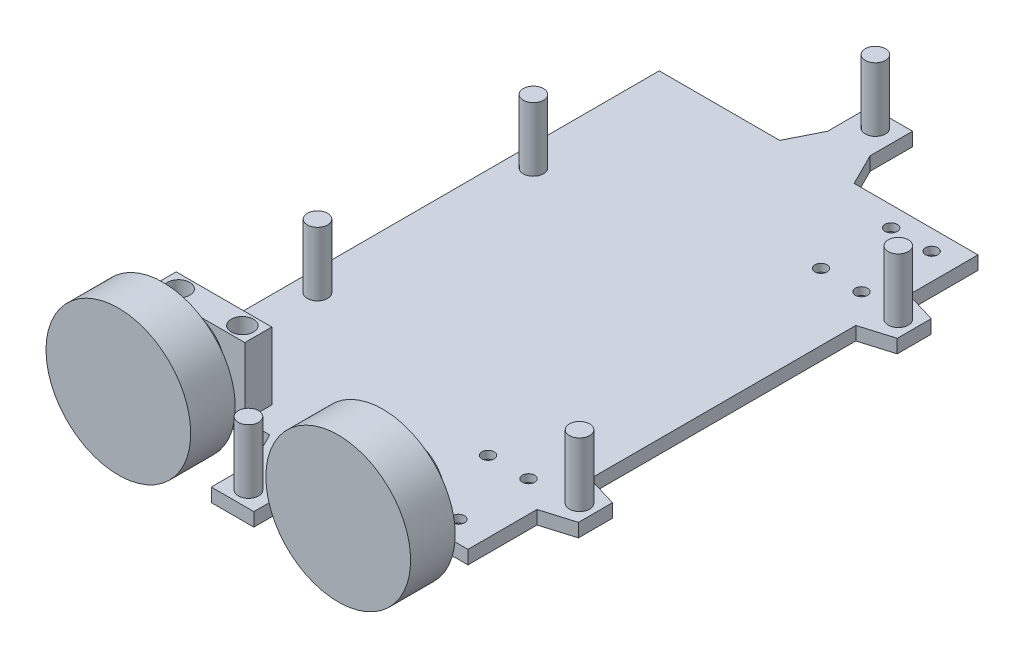
SolidWorks part; units mm, degrees
ref_plane "Front Plane" through (0, 0, 0) normal (0, 0, 1) x (1, 0, 0)
ref_plane "Top Plane" through (0, 0, 0) normal (0, 1, 0) x (1, 0, 0)
ref_plane "Right Plane" through (0, 0, 0) normal (1, 0, 0) x (0, 0, -1)
sketch "Sketch1" plane through (0, 0, 0) normal (0, 1, 0) x (1, 0, 0)
  line L0 (-87.7927, 0) -> (87.7927, 0) construction
  line L5 (-87.7927, 165.1) -> (87.7927, 165.1)
  line L6 (-87.7927, 165.1) -> (-87.7927, -165.1)
  line L7 (-87.7927, -165.1) -> (87.7927, -165.1)
  line L8 (87.7927, 165.1) -> (87.7927, -165.1)
  line L9 (0, 165.1) -> (0, -165.1) construction
  line L10 (-87.7927, 101.6) -> (-392.5927, 101.6)
  line L11 (-87.7927, -101.6) -> (-392.5927, -101.6)
  line L12 (-392.5927, -101.6) -> (-346.8735, -81.6)
  line L13 (-346.8735, -81.6) -> (-346.8735, -90.3491)
  line L14 (-346.8735, -90.3491) -> (-317.1033, -90.3491)
  line L15 (-317.1033, -90.3491) -> (-297.1033, -81.6)
  line L16 (-297.1033, -81.6) -> (-297.1033, -90.3491)
  line L17 (-297.1033, -90.3491) -> (-267.3331, -90.3491)
  line L18 (-267.3331, -90.3491) -> (-247.3331, -81.6)
  line L19 (-247.3331, -81.6) -> (-247.3331, -90.3491)
  line L20 (-247.3331, -90.3491) -> (-217.5629, -90.3491)
  line L21 (-217.5629, -90.3491) -> (-197.5629, -81.6)
  line L22 (-197.5629, -81.6) -> (-197.5629, -90.3491)
  line L23 (-197.5629, -90.3491) -> (-167.7927, -90.3491)
  line L24 (-167.7927, -90.3491) -> (-137.7927, -81.6)
  line L25 (-137.7927, -81.6) -> (-137.7927, -90.3491)
  line L26 (-137.7927, -90.3491) -> (-87.7927, -90.3491)
  line L27 (-137.7927, 90.3491) -> (-87.7927, 90.3491)
  line L28 (-197.5629, 90.3491) -> (-167.7927, 90.3491)
  line L29 (-137.7927, 81.6) -> (-137.7927, 90.3491)
  line L30 (-167.7927, 90.3491) -> (-137.7927, 81.6)
  line L31 (-197.5629, 81.6) -> (-197.5629, 90.3491)
  line L32 (-217.5629, 90.3491) -> (-197.5629, 81.6)
  line L33 (-247.3331, 90.3491) -> (-217.5629, 90.3491)
  line L34 (-247.3331, 81.6) -> (-247.3331, 90.3491)
  line L35 (-267.3331, 90.3491) -> (-247.3331, 81.6)
  line L36 (-297.1033, 90.3491) -> (-267.3331, 90.3491)
  line L37 (-297.1033, 81.6) -> (-297.1033, 90.3491)
  line L38 (-317.1033, 90.3491) -> (-297.1033, 81.6)
  line L39 (-346.8735, 90.3491) -> (-317.1033, 90.3491)
  line L40 (-346.8735, 81.6) -> (-346.8735, 90.3491)
  line L41 (-392.5927, 101.6) -> (-346.8735, 81.6)
  line L42 (78.4937, -130.8116) -> (78.4937, -151.8116)
  line L43 (-77.9683, 151.8116) -> (-27.1683, 151.8116)
  line L44 (-77.9683, 151.8116) -> (-77.9683, 130.8116)
  line L45 (-77.9683, 130.8116) -> (-27.1683, 130.8116)
  line L46 (-27.1683, 151.8116) -> (-27.1683, 130.8116)
  line L47 (27.6937, 130.8116) -> (78.4937, 130.8116)
  line L48 (27.6937, 130.8116) -> (27.6937, 151.8116)
  line L49 (27.6937, 151.8116) -> (78.4937, 151.8116)
  line L50 (78.4937, 130.8116) -> (78.4937, 151.8116)
  line L51 (27.6937, -151.8116) -> (78.4937, -151.8116)
  line L52 (27.6937, -130.8116) -> (27.6937, -151.8116)
  line L53 (27.6937, -130.8116) -> (78.4937, -130.8116)
  line L54 (-27.1683, -151.8116) -> (-27.1683, -130.8116)
  line L55 (-77.9683, -130.8116) -> (-27.1683, -130.8116)
  line L56 (-77.9683, -151.8116) -> (-77.9683, -130.8116)
  line L57 (-77.9683, -151.8116) -> (-27.1683, -151.8116)
  line L58 (53.0937, 157.0084) -> (53.0937, 28.6084) construction
  line L59 (34.0437, 112.3084) -> (72.1437, 112.3084)
  line L60 (34.0437, 112.3084) -> (34.0437, 28.6084)
  line L61 (34.0437, 28.6084) -> (72.1437, 28.6084)
  line L62 (72.1437, 112.3084) -> (72.1437, 28.6084)
  line L63 (46.2787, 112.3084) -> (59.9087, 112.3084)
  line L64 (46.2787, 112.3084) -> (46.2787, 157.0084)
  line L65 (46.2787, 157.0084) -> (59.9087, 157.0084)
  line L66 (59.9087, 112.3084) -> (59.9087, 157.0084)
  line L67 (46.2787, -157.0084) -> (59.9087, -157.0084)
  line L68 (-15.9616, 13.0957) -> (67.0384, 13.0957)
  line L69 (-15.9616, 13.0957) -> (-15.9616, -24.9043)
  line L70 (-15.9616, -24.9043) -> (67.0384, -24.9043)
  line L71 (67.0384, 13.0957) -> (67.0384, -24.9043)
  line L72 (-80.3064, 106.623) -> (-46.3064, 106.623)
  line L73 (-80.3064, 106.623) -> (-80.3064, 66.623)
  line L74 (-80.3064, 66.623) -> (-46.3064, 66.623)
  line L75 (-46.3064, 106.623) -> (-46.3064, 66.623)
  line L76 (53.0937, -157.0084) -> (53.0937, -28.6084) construction
  line L77 (59.9087, -112.3084) -> (59.9087, -157.0084)
  line L78 (46.2787, -112.3084) -> (46.2787, -157.0084)
  line L79 (46.2787, -112.3084) -> (59.9087, -112.3084)
  line L80 (72.1437, -112.3084) -> (72.1437, -28.6084)
  line L81 (34.0437, -28.6084) -> (72.1437, -28.6084)
  line L82 (34.0437, -112.3084) -> (34.0437, -28.6084)
  line L83 (34.0437, -112.3084) -> (72.1437, -112.3084)
  line L84 (-46.3064, -106.623) -> (-46.3064, -66.623)
  line L85 (-80.3064, -66.623) -> (-46.3064, -66.623)
  line L86 (-80.3064, -106.623) -> (-80.3064, -66.623)
  line L87 (-80.3064, -106.623) -> (-46.3064, -106.623)
  line L88 (-75.0927, 152.4) -> (75.0927, 152.4)
  line L89 (75.0927, 152.4) -> (75.0927, -152.4)
  line L90 (-75.0927, -152.4) -> (75.0927, -152.4)
  line L91 (-75.0927, 152.4) -> (-75.0927, -152.4)
  line L92 (53.0937, 28.6084) -> (53.0937, -28.6084) construction
  dimension "D1" = 304.8
  dimension "D2" = 203.2
  dimension "D3" = 21
  dimension "D4" = 50.8
  dimension "D5" = 330.2
  dimension "D6" = 20
  dimension "D7" = 20
  dimension "D8" = 30
  dimension "D9" = 50
  dimension "D10" = 38.1
  dimension "D11" = 83.7
  dimension "D12" = 44.7
  dimension "D13" = 13.63
  dimension "D14" = 175.5853
  dimension "D15" = 83
  dimension "D16" = 38
  dimension "D17" = 34
  dimension "D18" = 40
  dimension "D19" = 12.7
sketch "Sketch6" plane through (0, 0, 0) normal (0, 0, 1) x (1, 0, 0)
  line L0 (34.0437, 19.05) -> (72.1437, -19.05) construction
  line L1 (34.0437, 19.05) -> (72.1437, 19.05)
  line L2 (34.0437, 19.05) -> (34.0437, -19.05)
  line L3 (34.0437, -19.05) -> (72.1437, -19.05)
  line L4 (72.1437, 19.05) -> (72.1437, -19.05)
  line L5 (34.0437, -19.05) -> (72.1437, 19.05) construction
  line L6 (53.0937, 0) -> (-203.3411, 0) construction
  line L7 (-87.7927, 0) -> (-392.5927, 0) construction
  circle A0 centre (53.0937, 0) radius 34.05
  point P6 (53.0937, 0)
  dimension "D2" = 15
  dimension "D3" = 68.1
  dimension "D1" = 38.1
sketch "Sketch3" plane through (0, 0, 0) normal (0, 1, 0) x (1, 0, 0)
  line L0 (-87.7927, 0) -> (87.7927, 0) construction
  line L1 (-75, 120) -> (75, 120)
  line L2 (-75, 120) -> (-75, -120)
  line L3 (-75, -120) -> (75, -120)
  line L4 (75, 120) -> (75, -120)
  line L5 (0, 0) -> (0, 48.434) construction
  line L6 (43.5687, 110.5679) -> (62.6187, 110.5679) construction
  line L7 (43.5687, 110.5679) -> (43.5687, 77.5479) construction
  line L8 (43.5687, 77.5479) -> (62.6187, 77.5479) construction
  line L9 (62.6187, 110.5679) -> (62.6187, 77.5479) construction
  line L10 (53.0937, 110.5679) -> (53.0937, 77.5479) construction
  line L11 (53.0937, 157.0084) -> (53.0937, 28.6084) construction
  line L12 (41.425, -110) -> (60.475, -110) construction
  line L13 (41.425, -110) -> (41.425, -76.98) construction
  line L14 (60.475, -110) -> (60.475, -76.98) construction
  line L15 (41.425, -76.98) -> (60.475, -76.98) construction
  line L16 (31.9, -73.98) -> (70, -73.98) construction
  line L17 (31.9, -73.98) -> (31.9, -113) construction
  line L18 (31.9, -113) -> (70, -113) construction
  line L19 (70, -73.98) -> (70, -113) construction
  line L20 (16.9, -136) -> (85, -136)
  line L21 (-52.5, -107.3) -> (-52.5, -120) construction
  line L22 (-75, -120) -> (-30, -120)
  line L23 (-75, -120) -> (-75, -107.3)
  line L24 (-75, -107.3) -> (-30, -107.3)
  line L25 (-30, -120) -> (-30, -107.3)
  line L26 (16.9, -136) -> (16.9, -157)
  line L27 (-58.85, -113.65) -> (-46.15, -113.65) construction
  line L28 (-58.85, -113.65) -> (-58.85, -120) construction
  line L29 (-58.85, -120) -> (-46.15, -120)
  line L30 (-46.15, -113.65) -> (-46.15, -120) construction
  line L31 (50.95, -73.98) -> (50.95, -113) construction
  line L32 (16.9, -157) -> (85, -157)
  line L33 (85, -136) -> (85, -157)
  line L34 (19.0437, 0) -> (87.1437, 0) construction
  line L35 (50.95, -136) -> (50.95, -157)
  line L36 (-86.55, -136) -> (-18.45, -136)
  line L37 (-86.55, -136) -> (-86.55, -157)
  line L38 (-86.55, -157) -> (-18.45, -157)
  line L39 (-18.45, -136) -> (-18.45, -157)
  line L40 (-52.5, -136) -> (-52.5, -157)
  line L41 (-30, -113.65) -> (-37.5, -113.65) construction
  line L42 (-52.5, -123) -> (-52.5, -136)
  line L43 (-68.75, -136) -> (-36.25, -136)
  line L44 (-68.75, -136) -> (-68.75, -123)
  line L45 (-68.75, -123) -> (-36.25, -123)
  line L46 (-36.25, -136) -> (-36.25, -123)
  line L47 (34.7, -136) -> (67.2, -136)
  line L48 (34.7, -136) -> (34.7, -123)
  line L49 (34.7, -123) -> (67.2, -123)
  line L50 (67.2, -136) -> (67.2, -123)
  line L51 (50.95, -123) -> (50.95, -136)
  circle A0 centre (-67.5, -113.65) radius 2.5
  circle A1 centre (-67.5, -113.65) radius 4.75 construction
  circle A2 centre (-37.5, -113.65) radius 2.5
  dimension "D10" = 5
  dimension "D11" = 9.5
  dimension "D12" = 15
  dimension "D1" = 33.02
  dimension "D2" = 19.05
  dimension "D3" = 3
  dimension "D4" = 3
  dimension "D5" = 12.7
  dimension "D6" = 6.35
  dimension "D7" = 12.7
  dimension "D8" = 10
  dimension "D9" = 0
  dimension "D13" = 45
  dimension "D14" = 0
  dimension "D15" = 38.1
  dimension "D16" = 19.05
  dimension "D17" = 68.1
  dimension "D18" = 68.1
  dimension "D19" = 240
  dimension "D20" = 150
  dimension "D21" = 5
  dimension "D22" = 39.02
  dimension "D23" = 33.02
  dimension "D24" = 13
  dimension "D25" = 21
  dimension "D26" = 32.5
  dimension "D27" = 3
extrude "Boss-Extrude1" add sketch "Sketch3" against normal blind 6.35 from vertex contours L3 L4 L1 L2 starting at point (34.0437, -19.05, 0)
hole_wizard "CBORE for M5 SBHCS1" positions "Sketch4" profile "Sketch5" counterbore size "M5" standard "ANSI Metric" end condition through all
sketch "Sketch4" plane through (0, -25.4, 0) normal (0, 1, 0) x (1, 0, 0)
  point P0 (60.475, -76.98)
  point P3 (41.425, -76.98)
  point P6 (41.425, -110)
  point P9 (60.475, -110)
  point P12 (62.6187, 77.5479)
  point P15 (43.5687, 77.5479)
  point P18 (62.6187, 110.5679)
  point P21 (43.5687, 110.5679)
sketch "Sketch5" plane through (60.475, -25.4, 76.98) normal (1, 0, 0) x (0, 0, -1)
  line L0 (0, 0) -> (0, 6.35)
  line L1 (0, 6.35) -> (2.9, 6.35)
  line L3 (2.9, 6.35) -> (2.9, 2.75)
  line L4 (2.9, 2.75) -> (5.25, 2.75)
  line L5 (5.25, 2.75) -> (5.25, 0)
  line L7 (5.25, 0) -> (0, 0)
  line L11 (0, -6.35) -> (0, 107.95) construction
  dimension "Thru Hole Dia." = 5.8
  dimension "Thru Hole Depth" = 6.35
  dimension "C'Bore Dia." = 10.5
  dimension "C'Bore Depth" = 2.75
extrude "Boss-Extrude2" add sketch "Sketch3<4>" along normal blind 31.75 from surface separate body contours L23 L24 L25 L22 starting at face at (60.475, -19.05, 74.08)
sketch "Sketch3<4>" plane through (0, 0, 0) normal (0, 1, 0) x (1, 0, 0) same geometry as "Sketch3"
hole_wizard "CBORE for M5 SBHCS2" positions "Sketch7" profile "Sketch8" counterbore size "M5" standard "ANSI Metric" end condition through all
sketch "Sketch7" plane through (0, 12.7, 0) normal (0, 1, 0) x (1, 0, 0)
  point P0 (-37.5, -113.65)
  point P3 (-67.5, -113.65)
sketch "Sketch8" plane through (-37.5, 12.7, 113.65) normal (1, 0, 0) x (0, 0, 1)
  line L0 (0, 0) -> (0, 38.1)
  line L1 (0, 38.1) -> (2.9, 38.1)
  line L3 (2.9, 38.1) -> (2.9, 12.75)
  line L4 (2.9, 12.75) -> (5.25, 12.75)
  line L5 (5.25, 12.75) -> (5.25, 0)
  line L7 (5.25, 0) -> (0, 0)
  line L11 (0, -6.35) -> (0, 107.95) construction
  dimension "Thru Hole Dia." = 5.8
  dimension "Thru Hole Depth" = 38.1
  dimension "C'Bore Dia." = 10.5
  dimension "C'Bore Depth" = 12.75
hole_wizard "3/8-16 Tapped Hole1" positions "Sketch9" profile "Sketch10" tap size "3/8-16" standard "ANSI Inch" end condition through all
sketch "Sketch9" plane through (0, 0, 120) normal (0, 0, 1) x (1, 0, 0)
  point P0 (-52.5, 0)
sketch "Sketch10" plane through (-52.5, 0, 120) normal (1, 0, 0) x (0, -1, 0)
  line L0 (0, 0) -> (0, 240)
  line L1 (0, 240) -> (3.9687, 240)
  line L2 (3.9687, 240) -> (3.9687, 0)
  line L5 (3.9687, 0) -> (0, 0)
  line L11 (0, -6.35) -> (0, 107.95) construction
  dimension "Thru Tap Drill Dia." = 7.9375
  dimension "Thru Tap Drill Depth" = 240
cosmetic thread "Hole Thread1" parameters "D2"=9.525
hole_wizard "1/2 (0.5) Diameter Hole1" positions "Sketch11" profile "Sketch12" hole size "1/2" standard "ANSI Inch"
sketch "Sketch11" plane through (0, 0, 120) normal (0, 0, 1) x (1, 0, 0)
  point P0 (-52.5, 0)
sketch "Sketch12" plane through (-52.5, 0, 120) normal (1, 0, 0) x (0, -1, 0)
  line L0 (0, 0) -> (0, 10.1655)
  line L1 (0, 10.1655) -> (6.35, 6.35)
  line L2 (6.35, 6.35) -> (6.35, 0)
  line L5 (6.35, 0) -> (0, 0)
  line L10 (0, 10.1655) -> (-6.35, 6.35) construction
  line L11 (0, -6.35) -> (0, 107.95) construction
  dimension "Hole Dia." = 12.7
  dimension "Hole Depth" = 6.35
  dimension "Drill Angle" = 118
sketch "Sketch13" plane through (0, 0, 0) normal (0, 1, 0) x (1, 0, 0)
  line L0 (53.0937, 0) -> (-203.3411, 0) construction
  line L1 (0, 0) -> (-119.925, 0) construction
  line L2 (-75, 120) -> (-75, -120) construction
  line L3 (75, 120) -> (75, -120) construction
  line L4 (75, -87.5) -> (90, -83)
  line L5 (90, -83) -> (90, -67)
  line L6 (90, -67) -> (75, -62.5)
  line L7 (75, -75) -> (90, -75) construction
  line L9 (75, -62.5) -> (75, -87.5)
  line L10 (-52.5, -107.3) -> (-52.5, -91.4601) construction
  line L11 (50.95, -113) -> (50.95, -100.3386) construction
  line L14 (-0.775, -120) -> (-0.775, -155) construction
  line L15 (-75, -120) -> (75, -120) construction
  line L16 (-18.275, -120) -> (-10.775, -135)
  line L17 (-10.775, -135) -> (-10.775, -155)
  line L18 (-10.775, -155) -> (9.225, -155)
  line L19 (9.225, -155) -> (9.225, -135)
  line L20 (9.225, -135) -> (16.725, -120)
  line L21 (-18.275, -120) -> (16.725, -120)
  line L22 (75, 75) -> (90, 75) construction
  line L23 (75, 62.5) -> (75, 87.5)
  line L24 (90, 67) -> (75, 62.5)
  line L25 (90, 83) -> (90, 67)
  line L26 (75, 87.5) -> (90, 83)
  line L27 (-0.775, 120) -> (-0.775, 155) construction
  line L28 (-18.275, 120) -> (16.725, 120)
  line L29 (9.225, 135) -> (16.725, 120)
  line L30 (9.225, 155) -> (9.225, 135)
  line L31 (-10.775, 155) -> (9.225, 155)
  line L32 (-10.775, 135) -> (-10.775, 155)
  line L33 (-18.275, 120) -> (-10.775, 135)
  line L34 (50.95, -73.98) -> (50.95, -113) construction
  circle A1 centre (-65, 0) radius 4.7625 construction
  circle A3 centre (82.5, -75) radius 4.7625
  circle A5 centre (-65, -50.8) radius 4.7625
  circle A6 centre (-65, 50.8) radius 4.7625
  circle A7 centre (-0.775, -147.5) radius 4.7625
  circle A8 centre (82.5, 75) radius 4.7625
  circle A9 centre (-0.775, 147.5) radius 4.7625
  point P27 (-10.9265, -135)
  point P28 (0, 0)
  point P29 (-17.6866, -120)
  dimension "D1" = 9.525
  dimension "D2" = 10
  dimension "D3" = 16
  dimension "D4" = 50.8
  dimension "D5" = 25
  dimension "D6" = 15
  dimension "D7" = 75
  dimension "D8" = 15
  dimension "D9" = 35
  dimension "D10" = 20
  dimension "D11" = 20
  dimension "D12" = 7.5
extrude "Boss-Extrude3" add sketch "Sketch13" against normal up to surface (25.4 mm away) from surface contours L31 L30 L29 L28 L33 L32 | L26 L25 L24 L23 | L6 L9 L4 L5 | L19 L20 L21 L16 L17 L18 up to face at (60.475, -25.4, 71.73) starting at face at (60.475, -19.05, 74.08)
revolve "Revolve1" add sketch "Sketch3<5>" angle 360 about L42 region at (-69.525, 0, 146.5) region at (-60.625, 0, 129.5)
sketch "Sketch3<5>" plane through (0, 0, 0) normal (0, 1, 0) x (1, 0, 0) same geometry as "Sketch3"
revolve "Revolve2" add sketch "Sketch3<6>" angle 360 about L51 region at (33.925, 0, 146.5) region at (42.825, 0, 129.5)
sketch "Sketch3<6>" plane through (0, 0, 0) normal (0, 1, 0) x (1, 0, 0) same geometry as "Sketch3"
extrude "Boss-Extrude4" add sketch "Sketch13<4>" along normal blind 30 from surface separate body contours A7 | A5 | A3 | A8 | A9 | A6 starting at face at (60.475, -19.05, 74.08)
sketch "Sketch13<4>" plane through (0, 0, 0) normal (0, 1, 0) x (1, 0, 0) same geometry as "Sketch13"
sketch "Sketch16" plane through (0, 0, 0) normal (0, 1, 0) x (1, 0, 0)
  line L0 (-86.0009, 0) -> (95.4028, 0) construction
  line L2 (-86.0009, 0) -> (-86.0009, -124.6)
  line L3 (53.0937, 0) -> (-203.3411, 0) construction
  line L4 (-86.0009, 0) -> (-76.0009, 0)
  line L5 (-76.0009, 0) -> (-76.0009, -27.6435)
  line L6 (-76.0009, -27.6435) -> (-49.9164, -39.0555)
  line L7 (-49.9164, -39.0555) -> (-49.9164, -62.5445)
  line L8 (-49.9164, -62.5445) -> (-76.946, -74.3699)
  line L9 (-76.946, -74.3699) -> (-76.946, -126.7142)
  line L10 (-65, -50.8) -> (-49.9164, -50.8) construction
  line L11 (-103.2039, -160.6854) -> (-103.2039, -133.7611)
  line L12 (-103.2039, -160.6854) -> (-87.7174, -173.4309)
  line L13 (-87.7174, -173.4309) -> (81.4985, -173.4309)
  line L14 (-103.2039, -133.7611) -> (-86.0009, -124.6)
  line L15 (-76.946, -126.7142) -> (-95.4282, -136.5564)
  line L16 (-95.4282, -136.5564) -> (-95.4282, -158.6101)
  line L17 (-95.4282, -158.6101) -> (-84.4257, -167.6652)
  line L18 (-84.4257, -167.6652) -> (-13.4793, -167.6652)
  line L19 (-13.4793, -167.6652) -> (-13.4793, -136.5564)
  line L20 (-13.4793, -136.5564) -> (11.1685, -136.5564)
  line L21 (11.1685, -136.5564) -> (11.1685, -167.8836)
  line L22 (11.1685, -167.8836) -> (81.4985, -167.8836)
  line L23 (95.4028, 0) -> (95.4028, -128.983)
  line L24 (84.3593, 0) -> (84.3593, -54.8148)
  line L25 (84.3593, -54.8148) -> (72.0654, -62.5445)
  line L26 (72.0654, -62.5445) -> (72.0654, -90.3727)
  line L27 (72.0654, -90.3727) -> (84.3593, -98.3165)
  line L28 (84.3593, -98.3165) -> (84.3593, -124.6)
  point P31 (95.4028, -128.983)
  dimension "D1" = 10
